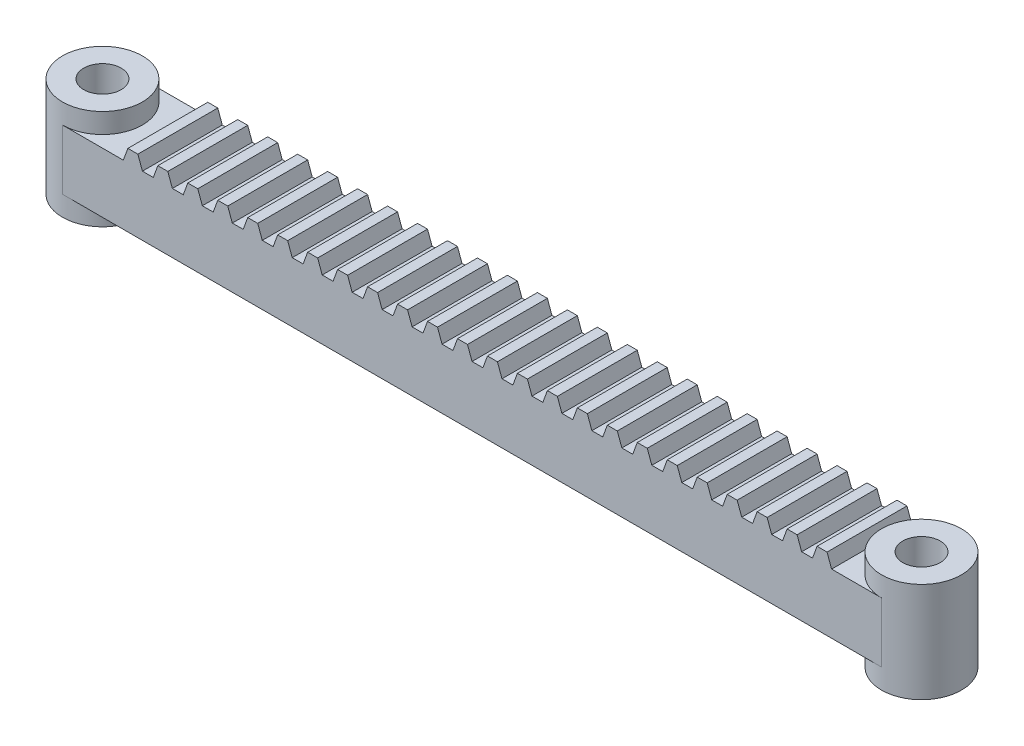
SolidWorks part; units mm, degrees
ref_plane "Front Plane" through (0, 0, 0) normal (0, 0, 1) x (1, 0, 0)
ref_plane "Top Plane" through (0, 0, 0) normal (0, 1, 0) x (1, 0, 0)
ref_plane "Right Plane" through (0, 0, 0) normal (1, 0, 0) x (0, 0, -1)
sketch "Sketch1" plane through (0, 0, 0) normal (0, 1, 0) x (1, 0, 0)
  line L1 (-82, 8) -> (82, 8)
  line L2 (-82, 8) -> (-82, -8)
  line L3 (-82, -8) -> (82, -8)
  line L4 (82, 8) -> (82, -8)
  line L5 (-82, 8) -> (82, -8) construction
  line L6 (-82, -8) -> (82, 8) construction
  circle A0 centre (82, 0) radius 8
  circle A1 centre (-82, 0) radius 8
  circle A2 centre (-82, 0) radius 3.75
  circle A3 centre (82, 0) radius 3.75
  point P0 (0, 0)
  dimension "D2" = 16
  dimension "D3" = 7.5
  dimension "D4" = 7.5
  dimension "D1" = 164
extrude "Boss-Extrude1" add sketch "Sketch1" along normal mid plane 12 contours A1 L3 A0 L1 region at (0, 0, 0)
extrude "Boss-Extrude2" add sketch "Sketch1<4>" along normal mid plane 20 contours A3 L4 A0 | A3 L4 A0 | A2 L2 A1 | A2 L2 A1 region at (-78.0968, 0, 0) region at (-85.9032, 0, 0) region at (85.9032, 0, 0) region at (78.0968, 0, 0)
sketch "Sketch1<4>" plane through (0, 0, 0) normal (0, 1, 0) x (1, 0, 0) same geometry as "Sketch1"
sketch "Sketch4" plane through (0, 0, 8) normal (0, 0, 1) x (1, 0, 0)
  line L0 (72, 6) -> (71.0901, 8.5)
  line L1 (-82, 6) -> (82, 6) construction
  line L2 (71.0901, 8.5) -> (69.0901, 8.5)
  line L3 (69.0901, 8.5) -> (68.1801, 6)
  line L4 (70.0901, 8.5) -> (70.0901, 6) construction
  line L5 (90, -10) -> (90, 10) construction
  line L6 (72, 6) -> (68.1801, 6)
  dimension "D1" = 40
  dimension "D2" = 2.5
  dimension "D3" = 2
  dimension "D4" = 18
extrude "Boss-Extrude4" add sketch "Sketch4" against normal blind 16
pattern_linear "LPattern1" count 24 spacing 6 along (-1, 0, 0) of "Boss-Extrude4"
